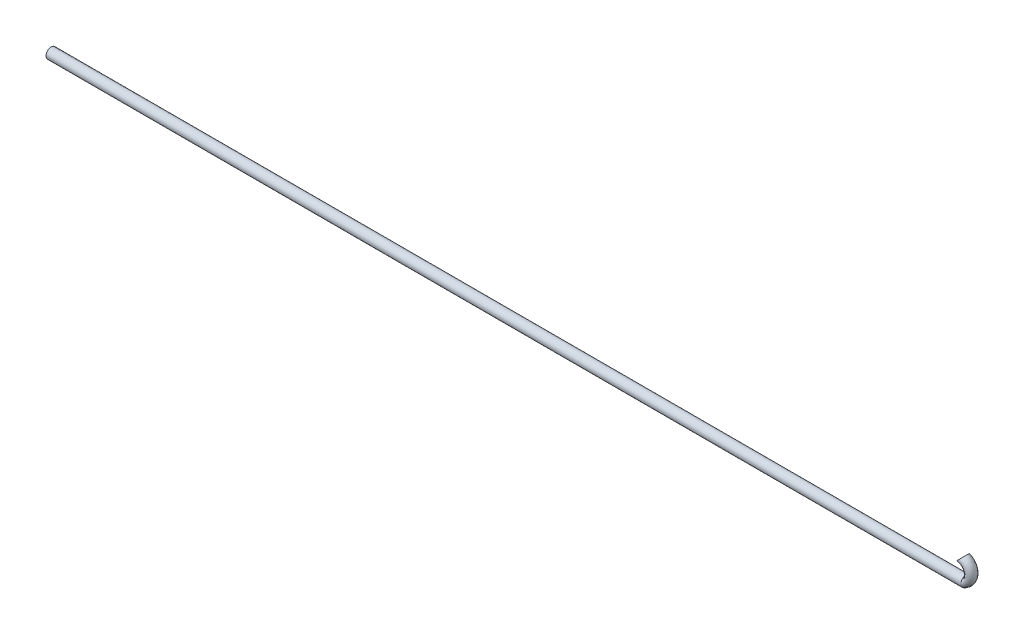
SolidWorks part; units mm, degrees
ref_plane "Front Plane" through (0, 0, 0) normal (0, 0, 1) x (1, 0, 0)
ref_plane "Top Plane" through (0, 0, 0) normal (0, 1, 0) x (1, 0, 0)
ref_plane "Right Plane" through (0, 0, 0) normal (1, 0, 0) x (0, 0, -1)
ref_axis "Axis1" through (-88.99, 0, 0) along (1, 0, 0)
sketch "Sketch1" plane through (0, 0, 0) normal (1, 0, 0) x (0, 0, -1)
  circle A0 centre (0, 0) radius 0.5143
  circle A1 centre (0, 0) radius 0.6223
  dimension "D1" = 1.0287
  dimension "D2" = 1.2446
extrude "Boss-Extrude1" add sketch "Sketch1" along normal blind 110
sketch "Sketch2" plane through (0, 0, 0) normal (0, 0, 1) x (1, 0, 0)
  line L1 (110, -0.6223) -> (110, 0.6223) construction
  line L2 (110, -0.6223) -> (110, 0.6223) construction
  arc A0 (110, 0) -> (109.6499, 2.3233) centre (109.3479, 1.0898) ccw
  point P2 (110, 0)
  point P6 (110, 0)
  dimension "D1" = 1.27
  dimension "D2" = 3
sketch "Sketch3" plane through (110, 0, 0) normal (1, 0, 0) x (0, 0, -1)
  circle A1 centre (0, 0) radius 0.6223 construction
  circle A2 centre (0, 0) radius 0.5143 construction
  circle A3 centre (0, 0) radius 0.6223
  circle A4 centre (0, 0) radius 0.5143
sweep "Sweep1" add profiles "Sketch3" path "Sketch2"
sketch "Sketch4" plane through (0, 0, 0) normal (0, 0, 1) x (1, 0, 0)
  line L0 (110.0873, 2.766) -> (110, -0.6223)
